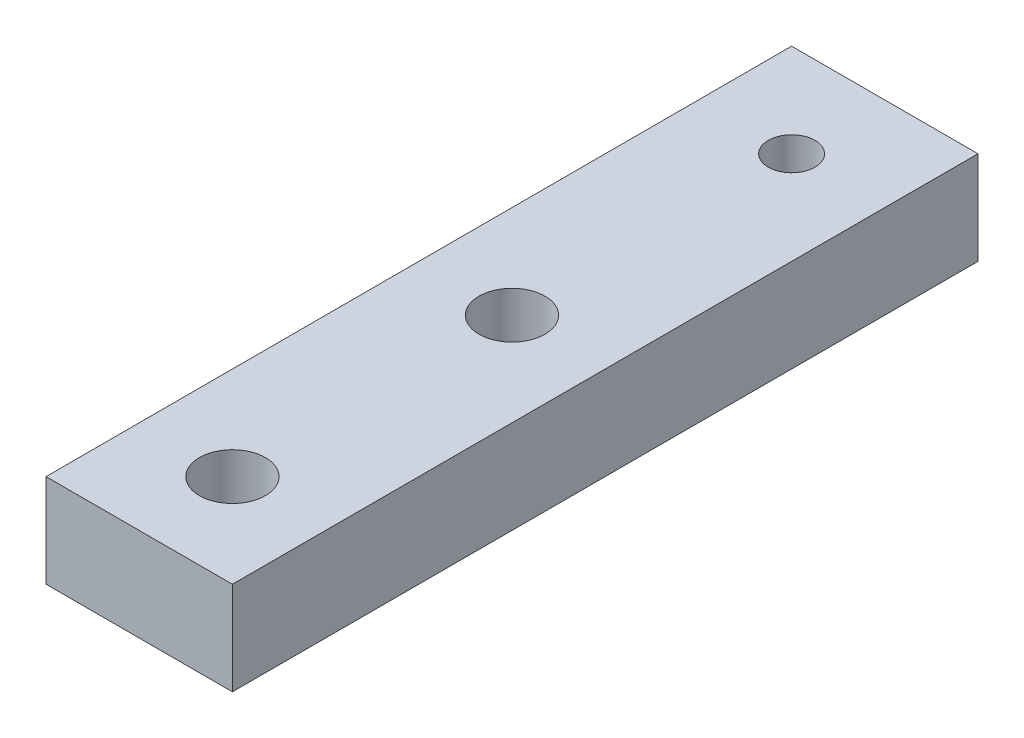
SolidWorks part; units mm, degrees
material "6061-T6 (SS)"
ref_plane "Front Plane" through (0, 0, 0) normal (0, 0, 1) x (1, 0, 0)
ref_plane "Top Plane" through (0, 0, 0) normal (0, 1, 0) x (1, 0, 0)
ref_plane "Right Plane" through (0, 0, 0) normal (1, 0, 0) x (0, 0, -1)
sketch "Sketch1" plane through (0, 0, 0) normal (0, 1, 0) x (1, 0, 0)
  line L1 (0, 0) -> (12.7, 0)
  line L2 (0, 0) -> (0, 50.8)
  line L3 (0, 50.8) -> (12.7, 50.8)
  line L4 (12.7, 0) -> (12.7, 50.8)
  dimension "D1" = 12.7
  dimension "D2" = 50.8
extrude "Boss-Extrude1" add sketch "Sketch1" along normal blind 6.35
sketch "Sketch9" plane through (0, 6.35, 0) normal (0, 1, 0) x (1, 0, 0)
  line L0 (0, 50.8) -> (6.35, 44.45) construction
  line L1 (6.35, 44.45) -> (12.7, 50.8) construction
  line L2 (12.7, 50.8) -> (0, 50.8) construction
  circle A0 centre (6.35, 44.45) radius 1.5875
  dimension "D1" = 3.175
  dimension "D2" = 6.35
extrude "Cut-Extrude1" cut sketch "Sketch9" against normal through all
hole_wizard "#8 Clearance Hole1" positions "Sketch10" profile "Sketch11" hole size "#8" standard "ANSI Inch" end condition through all
sketch "Sketch10" plane through (0, 6.35, 0) normal (0, 1, 0) x (1, 0, 0)
  line L0 (0, 0) -> (12.7, 0) construction
  line L1 (0, 0) -> (6.35, 6.35) construction
  line L2 (6.35, 6.35) -> (12.7, 0) construction
  point P0 (6.35, 25.4)
  point P2 (6.35, 6.35)
  dimension "D1" = 19.05
  dimension "D2" = 6.35
sketch "Sketch11" plane through (6.35, 6.35, -25.4) normal (1, 0, 0) x (0, 0, 1)
  line L0 (0, 0) -> (0, 6.35)
  line L1 (0, 6.35) -> (2.2479, 6.35)
  line L2 (2.2479, 6.35) -> (2.2479, 0)
  line L5 (2.2479, 0) -> (0, 0)
  line L11 (0, -6.35) -> (0, 107.95) construction
  dimension "Thru Hole Dia." = 4.4958
  dimension "Thru Hole Depth" = 6.35
